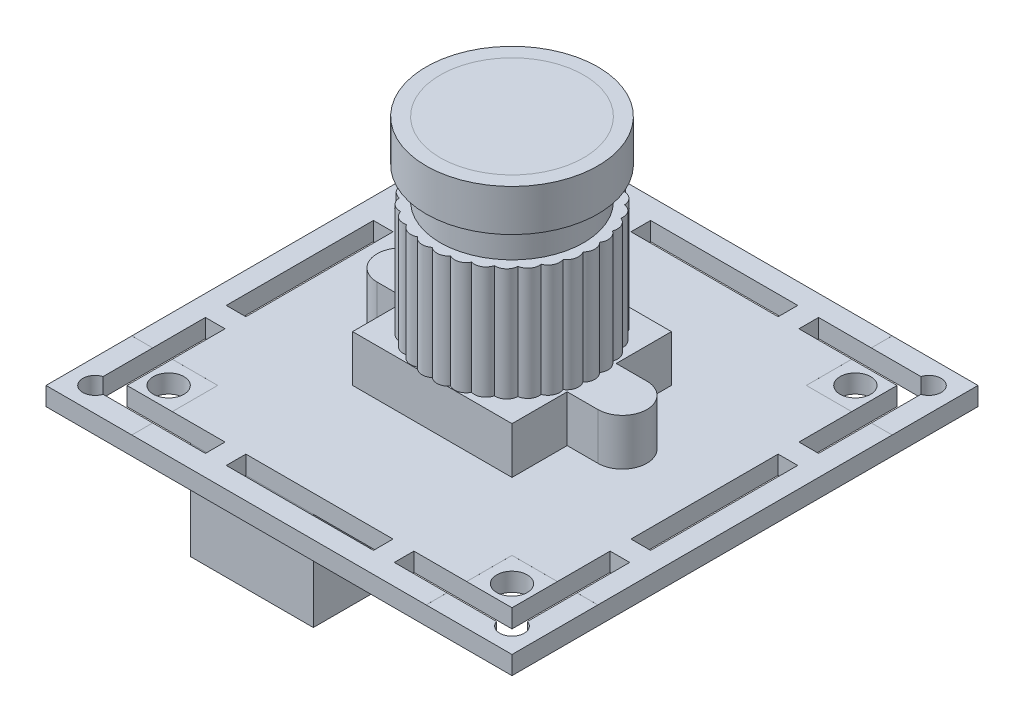
SolidWorks part; units mm, degrees
ref_plane "前视基准面" through (0, 0, 0) normal (0, 0, 1) x (1, 0, 0)
ref_plane "上视基准面" through (0, 0, 0) normal (0, 1, 0) x (1, 0, 0)
ref_plane "右视基准面" through (0, 0, 0) normal (1, 0, 0) x (0, 0, -1)
sketch "草图1" plane through (0, 0, 0) normal (0, 1, 0) x (1, 0, 0)
  line L0 (-14, 14) -> (14, 14) construction
  line L1 (19, -19) -> (-19, -19)
  line L2 (19, -19) -> (19, 19)
  line L3 (19, 19) -> (-19, 19)
  line L4 (-19, -19) -> (-19, 19)
  line L5 (19, -19) -> (-19, 19) construction
  line L6 (19, 19) -> (-19, -19) construction
  line L7 (14, 14) -> (14, -14) construction
  line L8 (14, -14) -> (-14, -14) construction
  line L9 (-14, -14) -> (-14, 14) construction
  line L10 (-17, 17) -> (17, 17) construction
  line L16 (17, 17) -> (17, -17) construction
  line L17 (17, -17) -> (-17, -17) construction
  line L18 (-17, -17) -> (-17, 17) construction
  circle A0 centre (-14, 14) radius 1.25
  circle A1 centre (-14, -14) radius 1.25
  circle A2 centre (14, 14) radius 1.25
  circle A3 centre (14, -14) radius 1.25
  circle A4 centre (-17, 17) radius 1
  circle A5 centre (-17, -17) radius 1
  circle A6 centre (17, -17) radius 1
  circle A7 centre (17, 17) radius 1
  point P0 (0, 0)
  dimension "D3" = 2.5
  dimension "D5" = 2
  dimension "D1" = 38
  dimension "D2" = 38
  dimension "D4" = 28
  dimension "D6" = 34
extrude "凸台-拉伸1" add sketch "草图1" along normal blind 1.5
sketch "草图9" plane through (0, 1.5, 0) normal (0, 1, 0) x (1, 0, 0)
  line L0 (12, 19) -> (12, 12)
  line L1 (-19, 19) -> (-12, 19)
  line L2 (-19, 19) -> (-19, 12)
  line L3 (-19, 12) -> (-12, 12)
  line L4 (-12, 19) -> (-12, 12)
  line L5 (19, 19) -> (12, 19)
  line L6 (19, 19) -> (19, 12)
  line L7 (19, 12) -> (12, 12)
  line L8 (19, -12) -> (12, -12)
  line L9 (19, -19) -> (19, -12)
  line L10 (19, -19) -> (12, -19)
  line L11 (12, -19) -> (12, -12)
  line L12 (-12, -19) -> (-12, -12)
  line L13 (-19, -19) -> (-12, -19)
  line L14 (-19, -19) -> (-19, -12)
  line L15 (-19, -12) -> (-12, -12)
  point P20 (0, 0)
  dimension "D1" = 7
  dimension "D2" = 7
  dimension "D3" = 4
extrude "切除-拉伸2" cut sketch "草图9" against normal blind 0.001
extrude "切除-拉伸3" cut sketch "草图9<2>" along normal blind 0.001 from surface starting at face at (0, 0, 0)
sketch "草图9<2>" plane through (0, 1.5, 0) normal (0, 1, 0) x (1, 0, 0) same geometry as "草图9"
sketch "草图2" plane through (0, 0, 0) normal (0, -1, 0) x (1, 0, 0)
  line L0 (-19, 19) -> (19, -19) construction
  line L1 (-19, -19) -> (19, 19) construction
  line L2 (-17.3, 17.3) -> (-7.7, 17.3)
  line L3 (-7.7, 17.3) -> (-7.7, 15.7)
  line L4 (-7.7, 15.7) -> (-15.7, 15.7)
  line L6 (-12, 19) -> (12, 19) construction
  line L7 (-19, -12) -> (-19, 12) construction
  line L8 (0, 15.7) -> (0, 17.3) construction
  line L9 (0, 17.3) -> (-6, 17.3)
  line L10 (-6, 17.3) -> (-6, 15.7)
  line L11 (-6, 15.7) -> (0, 15.7)
  line L12 (-15.7, 6) -> (-15.7, 0)
  line L13 (-17.3, 0) -> (-17.3, 6)
  line L14 (-17.3, 6) -> (-15.7, 6)
  line L15 (-17.3, 7.7) -> (-15.7, 7.7)
  line L16 (-15.7, 7.7) -> (-15.7, 15.7)
  line L17 (-17.3, 17.3) -> (-17.3, 7.7)
  line L18 (15.7, 7.7) -> (15.7, 15.7)
  line L19 (17.3, 17.3) -> (17.3, 7.7)
  line L20 (17.3, 7.7) -> (15.7, 7.7)
  line L21 (17.3, 6) -> (15.7, 6)
  line L22 (17.3, 0) -> (17.3, 6)
  line L23 (15.7, 6) -> (15.7, 0)
  line L24 (7.7, 15.7) -> (15.7, 15.7)
  line L25 (17.3, 17.3) -> (7.7, 17.3)
  line L26 (7.7, 17.3) -> (7.7, 15.7)
  line L27 (6, 17.3) -> (6, 15.7)
  line L28 (0, 17.3) -> (6, 17.3)
  line L29 (6, 15.7) -> (0, 15.7)
  line L30 (7.7, -15.7) -> (15.7, -15.7)
  line L31 (17.3, -17.3) -> (7.7, -17.3)
  line L32 (7.7, -17.3) -> (7.7, -15.7)
  line L33 (6, -17.3) -> (6, -15.7)
  line L34 (0, -17.3) -> (6, -17.3)
  line L35 (6, -15.7) -> (0, -15.7)
  line L36 (15.7, -7.7) -> (15.7, -15.7)
  line L37 (17.3, -17.3) -> (17.3, -7.7)
  line L38 (17.3, -7.7) -> (15.7, -7.7)
  line L39 (17.3, -6) -> (15.7, -6)
  line L40 (17.3, 0) -> (17.3, -6)
  line L41 (15.7, -6) -> (15.7, 0)
  line L42 (-15.7, -7.7) -> (-15.7, -15.7)
  line L43 (-17.3, -17.3) -> (-17.3, -7.7)
  line L44 (-17.3, -7.7) -> (-15.7, -7.7)
  line L45 (-17.3, -6) -> (-15.7, -6)
  line L46 (-17.3, 0) -> (-17.3, -6)
  line L47 (-15.7, -6) -> (-15.7, 0)
  line L48 (-7.7, -15.7) -> (-15.7, -15.7)
  line L49 (-17.3, -17.3) -> (-7.7, -17.3)
  line L50 (-7.7, -17.3) -> (-7.7, -15.7)
  line L51 (-6, -17.3) -> (-6, -15.7)
  line L52 (0, -17.3) -> (-6, -17.3)
  line L53 (-6, -15.7) -> (0, -15.7)
  point P14 (-7.7, 16.5)
  point P22 (-6, 16.5)
  point P74 (0, 0)
  dimension "D1" = 1.7
  dimension "D2" = 1.6
  dimension "D3" = 11.3
  dimension "D4" = 1.7
  dimension "D5" = 4
extrude "切除-拉伸1" cut sketch "草图2" against normal through all
sketch "草图3" plane through (0, 1.5, 0) normal (0, 1, 0) x (1, 0, 0)
  line L0 (-6.5, 2) -> (-6.5, 6.5)
  line L1 (6.5, -6.5) -> (-6.5, -6.5)
  line L2 (6.5, -6.5) -> (6.5, -2)
  line L3 (6.5, 6.5) -> (-6.5, 6.5)
  line L4 (-6.5, -6.5) -> (-6.5, -2)
  line L5 (6.5, -6.5) -> (-6.5, 6.5) construction
  line L6 (6.5, 6.5) -> (-6.5, -6.5) construction
  line L7 (9, -2) -> (6.5, -2)
  line L9 (9, 2) -> (6.5, 2)
  line L11 (11, -2) -> (-11, 2) construction
  line L12 (11, 2) -> (-11, -2) construction
  line L13 (-6.5, 2) -> (-9, 2)
  line L14 (-6.5, -2) -> (-9, -2)
  line L15 (6.5, 2) -> (6.5, 6.5)
  arc A0 (-9, 2) -> (-9, -2) centre (-9, 0) ccw
  arc A1 (9, -2) -> (9, 2) centre (9, 0) ccw
  point P0 (0, 0)
  point P6 (0, 0)
  dimension "D1" = 13
  dimension "D2" = 13
  dimension "D3" = 22
  dimension "D4" = 4
extrude "凸台-拉伸2" add sketch "草图3" along normal blind 3.8
sketch "草图4" plane through (0, 5.3, 0) normal (0, 1, 0) x (1, 0, 0)
  line L0 (0, 0) -> (0, 6.5) construction
  line L1 (0, 0) -> (1.3514, 6.358) construction
  circle A0 centre (0, 0) radius 6.5 construction
  circle A1 centre (0, 0) radius 6.75 construction
  arc A2 (1.3514, 6.358) -> (0, 6.5) centre (0.6062, 5.7673) ccw
  arc A3 (2.6438, 5.938) -> (1.3514, 6.358) centre (1.792, 5.5152) ccw
  arc A4 (3.8206, 5.2586) -> (2.6438, 5.938) centre (2.8995, 5.0221) ccw
  arc A5 (4.8304, 4.3493) -> (3.8206, 5.2586) centre (3.8803, 4.3095) ccw
  arc A6 (5.6292, 3.25) -> (4.8304, 4.3493) centre (4.6915, 3.4086) ccw
  arc A7 (6.1819, 2.0086) -> (5.6292, 3.25) centre (5.2977, 2.3587) ccw
  arc A8 (6.4644, 0.6794) -> (6.1819, 2.0086) centre (5.6723, 1.2057) ccw
  arc A9 (6.4644, -0.6794) -> (6.4644, 0.6794) centre (5.799, 0) ccw
  arc A10 (6.1819, -2.0086) -> (6.4644, -0.6794) centre (5.6723, -1.2057) ccw
  arc A11 (5.6292, -3.25) -> (6.1819, -2.0086) centre (5.2977, -2.3587) ccw
  arc A12 (4.8304, -4.3493) -> (5.6292, -3.25) centre (4.6915, -3.4086) ccw
  arc A13 (3.8206, -5.2586) -> (4.8304, -4.3493) centre (3.8803, -4.3095) ccw
  arc A14 (2.6438, -5.938) -> (3.8206, -5.2586) centre (2.8995, -5.0221) ccw
  arc A15 (1.3514, -6.358) -> (2.6438, -5.938) centre (1.792, -5.5152) ccw
  arc A16 (0, -6.5) -> (1.3514, -6.358) centre (0.6062, -5.7673) ccw
  arc A17 (-1.3514, -6.358) -> (0, -6.5) centre (-0.6062, -5.7673) ccw
  arc A18 (-2.6438, -5.938) -> (-1.3514, -6.358) centre (-1.792, -5.5152) ccw
  arc A19 (-3.8206, -5.2586) -> (-2.6438, -5.938) centre (-2.8995, -5.0221) ccw
  arc A20 (-4.8304, -4.3493) -> (-3.8206, -5.2586) centre (-3.8803, -4.3095) ccw
  arc A21 (-5.6292, -3.25) -> (-4.8304, -4.3493) centre (-4.6915, -3.4086) ccw
  arc A22 (-6.1819, -2.0086) -> (-5.6292, -3.25) centre (-5.2977, -2.3587) ccw
  arc A23 (-6.4644, -0.6794) -> (-6.1819, -2.0086) centre (-5.6723, -1.2057) ccw
  arc A24 (-6.4644, 0.6794) -> (-6.4644, -0.6794) centre (-5.799, 0) ccw
  arc A25 (-6.1819, 2.0086) -> (-6.4644, 0.6794) centre (-5.6723, 1.2057) ccw
  arc A26 (-5.6292, 3.25) -> (-6.1819, 2.0086) centre (-5.2977, 2.3587) ccw
  arc A27 (-4.8304, 4.3493) -> (-5.6292, 3.25) centre (-4.6915, 3.4086) ccw
  arc A28 (-3.8206, 5.2586) -> (-4.8304, 4.3493) centre (-3.8803, 4.3095) ccw
  arc A29 (-2.6438, 5.938) -> (-3.8206, 5.2586) centre (-2.8995, 5.0221) ccw
  arc A30 (-1.3514, 6.358) -> (-2.6438, 5.938) centre (-1.792, 5.5152) ccw
  arc A31 (0, 6.5) -> (-1.3514, 6.358) centre (-0.6062, 5.7673) ccw
  point P96 (0, 0)
  dimension "D1" = 12
  dimension "D2" = 13
  dimension "D3" = 13.5
  dimension "D4" = 30
extrude "凸台-拉伸3" add sketch "草图4" along normal blind 9.2
sketch "草图5" plane through (0, 14.5, 0) normal (0, 1, 0) x (1, 0, 0)
  circle A0 centre (0, 0) radius 5.85
  dimension "D1" = 11.7
extrude "凸台-拉伸4" add sketch "草图5" along normal blind 6
sketch "草图7" plane through (0, 20.5, 0) normal (0, 1, 0) x (1, 0, 0)
  circle A0 centre (0, 0) radius 7
  circle A1 centre (0, 0) radius 5.85
  dimension "D1" = 14
extrude "凸台-拉伸5" add sketch "草图7" against normal blind 3.4 separate body
sketch "草图8" plane through (0, 0, 0) normal (0, -1, 0) x (1, 0, 0)
  line L1 (-10.5, 15.7) -> (-0.5, 15.7)
  line L2 (-10.5, 15.7) -> (-10.5, 11)
  line L3 (-10.5, 11) -> (-0.5, 11)
  line L4 (-0.5, 15.7) -> (-0.5, 11)
  line L5 (-12, 15.7) -> (-7.7, 15.7) construction
  line L6 (-19, -12) -> (-19, 12) construction
  dimension "D1" = 10
  dimension "D2" = 4.7
  dimension "D3" = 8.5
extrude "凸台-拉伸6" add sketch "草图8" along normal blind 8 separate body
